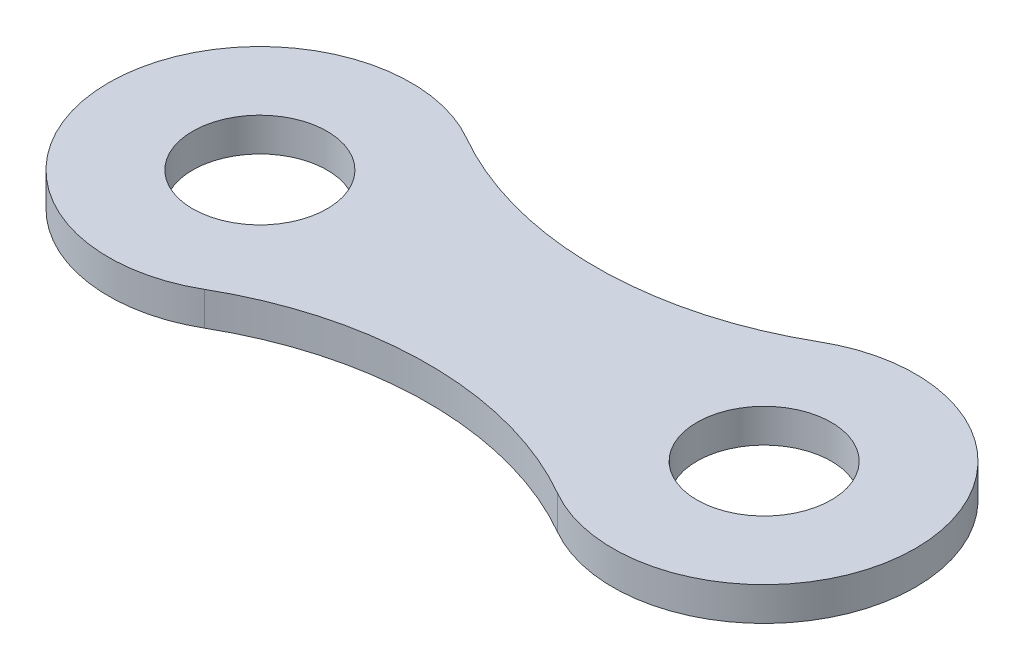
SolidWorks part; units mm, degrees
ref_plane "Ebene vorne" through (0, 0, 0) normal (0, 0, 1) x (1, 0, 0)
ref_plane "Ebene oben" through (0, 0, 0) normal (0, 1, 0) x (1, 0, 0)
ref_plane "Ebene rechts" through (0, 0, 0) normal (1, 0, 0) x (0, 0, -1)
sketch "Skizze2" plane through (0, 0, 0) normal (0, 1, 0) x (1, 0, 0)
  line L0 (0, 0) -> (0, 12.8795) construction
  circle A0 centre (-7.5, 0) radius 2
  circle A1 centre (7.5, 0) radius 2
  circle A2 centre (-7.5, 0) radius 4.5 construction
  circle A3 centre (7.5, 0) radius 4.5 construction
  arc A4 (-5.2545, 3.8997) -> (5.2545, 3.8997) centre (0, 13.0248) ccw
  arc A5 (-5.2545, -3.8997) -> (5.2545, -3.8997) centre (0, -13.0248) cw
  arc A6 (-5.2545, 3.8997) -> (-5.2545, -3.8997) centre (-7.5, 0) ccw
  arc A7 (5.2545, 3.8997) -> (5.2545, -3.8997) centre (7.5, 0) cw
  dimension "D1" = 4
  dimension "D3" = 9
  dimension "D2" = 15
sheet metal parameters "Blech1" thickness 1 parameters "D1"=1
base flange "Basis-Blech1" sketch "Skizze2" thickness 1 reverse thickness direction no parameters "D1"=1
sketch "Skizze5" plane through (0, 0, 0) normal (0, 1, 0) x (1, 0, 0)
  line L0 (2.3384, 2.7579) -> (2.3384, -2.7579)
  arc A2 (-5.2545, 3.8997) -> (5.2545, 3.8997) centre (0, 13.0248) ccw construction
  arc A3 (5.2545, -3.8997) -> (-5.2545, -3.8997) centre (0, -13.0248) ccw construction
sketched bend "Skizzierte Biegung1" [suppressed] parameters "D1"=1
bend "Skizzenbiegung1" bend radius 1 bend angle 90 parameters "D5"=1
flat pattern "Abwicklung1" [suppressed]
sketch "Biegung-Linien1" plane through (0, 0, 0) normal (0, 1, 0) x (-1, 0, 0)
sketch3d "Rahmen1" [suppressed]
  line L0 (15.75, -2.0124, 0) -> (-8.25, -2.0124, 0) construction
  line L1 (15.75, -11.0121, 0) -> (-8.25, -11.0121, 0) construction
  line L2 (15.75, -2.0124, 0) -> (15.75, -11.0121, 0) construction
  line L3 (-8.25, -2.0124, 0) -> (-8.25, -11.0121, 0) construction
bend of the flat pattern "Abwickeln-<Skizzenbiegung1>1"
